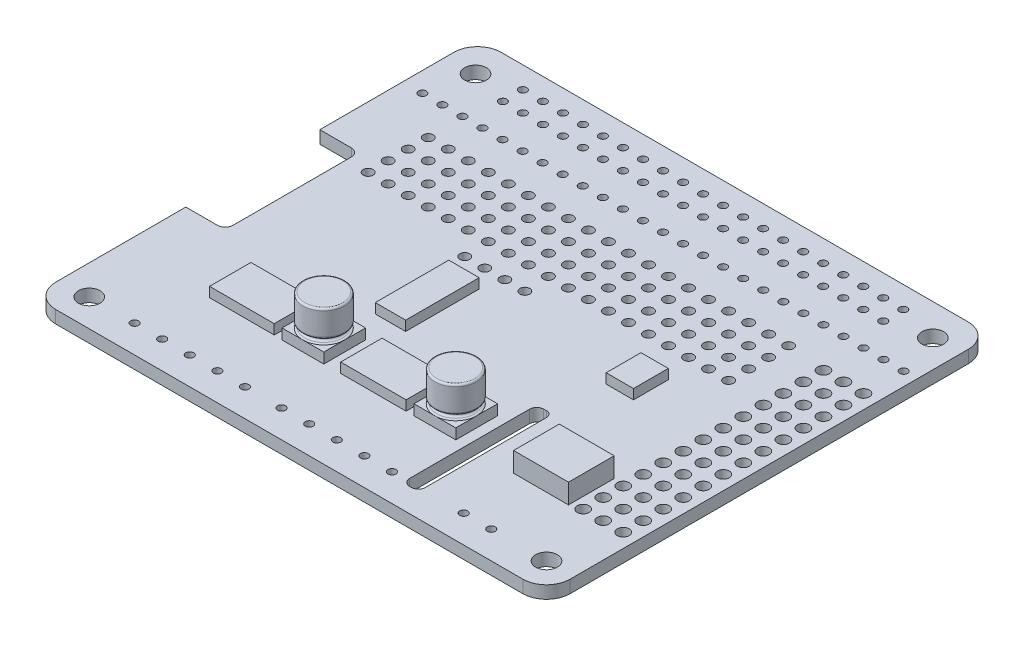
SolidWorks part; units mm, degrees
ref_plane "Front Plane" through (0, 0, 0) normal (0, 0, 1) x (1, 0, 0)
ref_plane "Top Plane" through (0, 0, 0) normal (0, 1, 0) x (1, 0, 0)
ref_plane "Right Plane" through (0, 0, 0) normal (1, 0, 0) x (0, 0, -1)
sketch "Sketch1" plane through (0, 0, 0) normal (0, 1, 0) x (1, 0, 0)
  line L1 (-72.0204, 27.4034) -> (-12.7704, 27.4034)
  line L2 (-75.0204, 24.4034) -> (-75.0204, -26.0966)
  line L3 (-72.0204, -29.0966) -> (-12.7704, -29.0966)
  line L4 (-9.7704, 24.4034) -> (-9.7704, -26.0966)
  line L5 (-75.0204, 7.4034) -> (-71.0204, 7.4034)
  line L6 (-75.0204, 7.4034) -> (-75.0204, -9.5966)
  line L7 (-75.0204, -9.5966) -> (-71.0204, -9.5966)
  line L8 (-70.0204, 6.4034) -> (-70.0204, -8.5966)
  line L9 (-29.7669, -9.0966) -> (-30.1204, -9.0966)
  line L10 (-29.0204, -9.8431) -> (-29.0204, -25.1966)
  line L11 (-29.9204, -26.0966) -> (-30.1204, -26.0966)
  line L12 (-31.0204, -9.9966) -> (-31.0204, -25.1966)
  arc A0 (-72.0204, -29.0966) -> (-75.0204, -26.0966) centre (-72.0204, -26.0966) cw
  arc A1 (-9.7704, -26.0966) -> (-12.7704, -29.0966) centre (-12.7704, -26.0966) cw
  arc A2 (-9.7704, 24.4034) -> (-12.7704, 27.4034) centre (-12.7704, 24.4034) ccw
  arc A3 (-72.0204, 27.4034) -> (-75.0204, 24.4034) centre (-72.0204, 24.4034) ccw
  arc A4 (-70.0204, -8.5966) -> (-71.0204, -9.5966) centre (-71.0204, -8.5966) cw
  arc A5 (-70.0204, 6.4034) -> (-71.0204, 7.4034) centre (-71.0204, 6.4034) ccw
  arc A6 (-29.0204, -25.1966) -> (-29.9204, -26.0966) centre (-29.9204, -25.1966) cw
  arc A7 (-30.1204, -26.0966) -> (-31.0204, -25.1966) centre (-30.1204, -25.1966) cw
  arc A8 (-30.1204, -9.0966) -> (-31.0204, -9.9966) centre (-30.1204, -9.9966) ccw
  arc A9 (-29.7669, -9.0966) -> (-29.0204, -9.8431) centre (-29.7669, -9.8431) cw
  circle A10 centre (-13.2704, -25.5966) radius 1.375
  circle A11 centre (-71.2704, -25.5966) radius 1.375
  circle A12 centre (-71.2704, 23.4034) radius 1.375
  circle A13 centre (-13.2704, 23.4034) radius 1.375
  point P6 (-75.0204, -29.0966)
  point P11 (-9.7704, 27.4034)
  point P14 (-75.0204, 27.4034)
  point P23 (-70.0204, 7.4034)
  point P30 (-29.0204, -26.0966)
  point P35 (-31.0204, -9.0966)
  point P38 (-29.0204, -9.0966)
  point P41 (0, 0)
  point P43 (0, 0)
  dimension "D3" = 3
  dimension "D7" = 1
  dimension "D12" = 0.9
  dimension "D13" = 0.7465
  dimension "D14" = 2.75
  dimension "D1" = 56.5
  dimension "D2" = 65.25
  dimension "D4" = 17
  dimension "D5" = 5
  dimension "D6" = 20
  dimension "D8" = 17
  dimension "D9" = 2
  dimension "D10" = 44
  dimension "D11" = 3
  dimension "D15" = 3.5
  dimension "D16" = 3.5
  dimension "D17" = 2
  dimension "D18" = 2
extrude "Board" add sketch "Sketch1" along normal blind 1.6 contours A5 L8 A4 L7 L2 A0 L3 A1 L4 A2 L1 A3 L5 A13 A12 A11 A10 L9 A9 L10 A6 L11 A7 L12 A8 region at (-41.7924, 0, 0.6811)
sketch "Sketch2" plane through (0, 1.6, 0) normal (0, 1, 0) x (1, 0, 0)
  line L8 (-70.0204, 6.4034) -> (-70.0204, -8.5966)
  line L9 (-71.0204, -9.5966) -> (-75.0204, -9.5966)
  line L10 (-75.0204, -9.5966) -> (-75.0204, -26.0966)
  line L11 (-72.0204, -29.0966) -> (-12.7704, -29.0966)
  line L12 (-9.7704, -26.0966) -> (-9.7704, 24.4034)
  line L13 (-12.7704, 27.4034) -> (-72.0204, 27.4034)
  line L14 (-75.0204, 24.4034) -> (-75.0204, 7.4034)
  line L15 (-75.0204, 7.4034) -> (-71.0204, 7.4034)
  line L16 (-70.0204, 6.4034) -> (-70.0204, -8.5966)
  line L17 (-71.0204, -9.5966) -> (-75.0204, -9.5966)
  line L18 (-75.0204, -9.5966) -> (-75.0204, -26.0966)
  line L19 (-72.0204, -29.0966) -> (-12.7704, -29.0966)
  line L20 (-9.7704, -26.0966) -> (-9.7704, 24.4034)
  line L21 (-12.7704, 27.4034) -> (-72.0204, 27.4034)
  line L22 (-75.0204, 24.4034) -> (-75.0204, 7.4034)
  line L23 (-75.0204, 7.4034) -> (-71.0204, 7.4034)
  circle A0 centre (-66.5204, 24.6534) radius 0.5
  circle A1 centre (-63.9804, 24.6534) radius 0.5
  circle A2 centre (-61.4404, 24.6534) radius 0.5
  circle A3 centre (-58.9004, 24.6534) radius 0.5
  circle A4 centre (-56.3604, 24.6534) radius 0.5
  circle A5 centre (-53.8204, 24.6534) radius 0.5
  arc A6 (-70.0204, 6.4034) -> (-71.0204, 7.4034) centre (-71.0204, 6.4034) ccw
  arc A7 (-71.0204, -9.5966) -> (-70.0204, -8.5966) centre (-71.0204, -8.5966) ccw
  arc A8 (-75.0204, -26.0966) -> (-72.0204, -29.0966) centre (-72.0204, -26.0966) ccw
  arc A9 (-12.7704, -29.0966) -> (-9.7704, -26.0966) centre (-12.7704, -26.0966) ccw
  arc A10 (-9.7704, 24.4034) -> (-12.7704, 27.4034) centre (-12.7704, 24.4034) ccw
  arc A11 (-72.0204, 27.4034) -> (-75.0204, 24.4034) centre (-72.0204, 24.4034) ccw
  arc A12 (-70.0204, 6.4034) -> (-71.0204, 7.4034) centre (-71.0204, 6.4034) ccw
  arc A13 (-71.0204, -9.5966) -> (-70.0204, -8.5966) centre (-71.0204, -8.5966) ccw
  arc A14 (-75.0204, -26.0966) -> (-72.0204, -29.0966) centre (-72.0204, -26.0966) ccw
  arc A15 (-12.7704, -29.0966) -> (-9.7704, -26.0966) centre (-12.7704, -26.0966) ccw
  arc A16 (-9.7704, 24.4034) -> (-12.7704, 27.4034) centre (-12.7704, 24.4034) ccw
  arc A17 (-72.0204, 27.4034) -> (-75.0204, 24.4034) centre (-72.0204, 24.4034) ccw
  circle A18 centre (-51.2804, 24.6534) radius 0.5
  circle A19 centre (-48.7404, 24.6534) radius 0.5
  circle A20 centre (-46.2004, 24.6534) radius 0.5
  circle A21 centre (-43.6604, 24.6534) radius 0.5
  circle A22 centre (-41.1204, 24.6534) radius 0.5
  circle A23 centre (-38.5804, 24.6534) radius 0.5
  circle A24 centre (-36.0404, 24.6534) radius 0.5
  circle A25 centre (-33.5004, 24.6534) radius 0.5
  circle A26 centre (-30.9604, 24.6534) radius 0.5
  circle A27 centre (-28.4204, 24.6534) radius 0.5
  circle A28 centre (-25.8804, 24.6534) radius 0.5
  circle A29 centre (-23.3404, 24.6534) radius 0.5
  circle A30 centre (-20.8004, 24.6534) radius 0.5
  circle A31 centre (-18.2604, 24.6534) radius 0.5
  circle A32 centre (-63.9804, 22.1134) radius 0.5
  circle A33 centre (-61.4404, 22.1134) radius 0.5
  circle A34 centre (-58.9004, 22.1134) radius 0.5
  circle A35 centre (-56.3604, 22.1134) radius 0.5
  circle A36 centre (-53.8204, 22.1134) radius 0.5
  circle A37 centre (-51.2804, 22.1134) radius 0.5
  circle A38 centre (-48.7404, 22.1134) radius 0.5
  circle A39 centre (-46.2004, 22.1134) radius 0.5
  circle A40 centre (-43.6604, 22.1134) radius 0.5
  circle A41 centre (-41.1204, 22.1134) radius 0.5
  circle A42 centre (-38.5804, 22.1134) radius 0.5
  circle A43 centre (-36.0404, 22.1134) radius 0.5
  circle A44 centre (-33.5004, 22.1134) radius 0.5
  circle A45 centre (-30.9604, 22.1134) radius 0.5
  circle A46 centre (-28.4204, 22.1134) radius 0.5
  circle A47 centre (-25.8804, 22.1134) radius 0.5
  circle A48 centre (-23.3404, 22.1134) radius 0.5
  circle A49 centre (-20.8004, 22.1134) radius 0.5
  circle A50 centre (-18.2604, 22.1134) radius 0.5
  circle A51 centre (-66.5204, 22.1134) radius 0.5
  circle A52 centre (-72.5204, 17.9034) radius 0.5
  circle A53 centre (-69.9766, 17.9034) radius 0.5
  circle A54 centre (-67.4329, 17.9034) radius 0.5
  circle A55 centre (-64.8891, 17.9034) radius 0.5
  circle A56 centre (-62.3454, 17.9034) radius 0.5
  circle A57 centre (-59.8016, 17.9034) radius 0.5
  circle A58 centre (-57.2579, 17.9034) radius 0.5
  circle A59 centre (-54.7141, 17.9034) radius 0.5
  circle A60 centre (-52.1704, 17.9034) radius 0.5
  circle A61 centre (-49.6266, 17.9034) radius 0.5
  circle A62 centre (-47.0829, 17.9034) radius 0.5
  circle A63 centre (-44.5391, 17.9034) radius 0.5
  circle A64 centre (-41.9954, 17.9034) radius 0.5
  circle A65 centre (-39.4516, 17.9034) radius 0.5
  circle A66 centre (-36.9079, 17.9034) radius 0.5
  circle A67 centre (-34.3641, 17.9034) radius 0.5
  circle A68 centre (-31.8204, 17.9034) radius 0.5
  circle A69 centre (-29.2766, 17.9034) radius 0.5
  circle A70 centre (-26.7329, 17.9034) radius 0.5
  circle A71 centre (-24.1891, 17.9034) radius 0.5
  circle A72 centre (-21.6454, 17.9034) radius 0.5
  circle A73 centre (-19.1016, 17.9034) radius 0.5
  circle A74 centre (-16.5579, 17.9034) radius 0.5
  circle A75 centre (-14.0141, 17.9034) radius 0.5
  circle A76 centre (-11.4704, 17.9034) radius 0.5
  circle A77 centre (-11.5604, 12.9034) radius 0.75
  circle A78 centre (-14.1004, 12.9034) radius 0.75
  circle A79 centre (-16.6404, 12.9034) radius 0.75
  circle A80 centre (-14.1004, 10.3634) radius 0.75
  circle A81 centre (-16.6404, 10.3634) radius 0.75
  circle A82 centre (-14.1004, 7.8234) radius 0.75
  circle A83 centre (-16.6404, 7.8234) radius 0.75
  circle A84 centre (-14.1004, 5.2834) radius 0.75
  circle A85 centre (-16.6404, 5.2834) radius 0.75
  circle A86 centre (-14.1004, 2.7434) radius 0.75
  circle A87 centre (-16.6404, 2.7434) radius 0.75
  circle A88 centre (-14.1004, 0.2034) radius 0.75
  circle A89 centre (-16.6404, 0.2034) radius 0.75
  circle A90 centre (-14.1004, -2.3366) radius 0.75
  circle A91 centre (-16.6404, -2.3366) radius 0.75
  circle A92 centre (-14.1004, -4.8766) radius 0.75
  circle A93 centre (-16.6404, -4.8766) radius 0.75
  circle A94 centre (-14.1004, -7.4166) radius 0.75
  circle A95 centre (-16.6404, -7.4166) radius 0.75
  circle A96 centre (-14.1004, -9.9566) radius 0.75
  circle A97 centre (-16.6404, -9.9566) radius 0.75
  circle A98 centre (-14.1004, -12.4966) radius 0.75
  circle A99 centre (-16.6404, -12.4966) radius 0.75
  circle A100 centre (-14.1004, -15.0366) radius 0.75
  circle A101 centre (-16.6404, -15.0366) radius 0.75
  circle A102 centre (-14.1004, -17.5766) radius 0.75
  circle A103 centre (-16.6404, -17.5766) radius 0.75
  circle A104 centre (-11.5604, 10.3634) radius 0.75
  circle A105 centre (-11.5604, 7.8234) radius 0.75
  circle A106 centre (-11.5604, 5.2834) radius 0.75
  circle A107 centre (-11.5604, 2.7434) radius 0.75
  circle A108 centre (-11.5604, 0.2034) radius 0.75
  circle A109 centre (-11.5604, -2.3366) radius 0.75
  circle A110 centre (-11.5604, -4.8766) radius 0.75
  circle A111 centre (-11.5604, -7.4166) radius 0.75
  circle A112 centre (-11.5604, -9.9566) radius 0.75
  circle A113 centre (-11.5604, -12.4966) radius 0.75
  circle A114 centre (-11.5604, -15.0366) radius 0.75
  circle A115 centre (-11.5604, -17.5766) radius 0.75
  circle A116 centre (-67.2704, 13.4034) radius 0.625
  circle A117 centre (-64.7304, 13.4034) radius 0.625
  circle A118 centre (-62.1904, 13.4034) radius 0.625
  circle A119 centre (-59.6504, 13.4034) radius 0.625
  circle A120 centre (-57.1104, 13.4034) radius 0.625
  circle A121 centre (-54.5704, 13.4034) radius 0.625
  circle A122 centre (-52.0304, 13.4034) radius 0.625
  circle A123 centre (-49.4904, 13.4034) radius 0.625
  circle A124 centre (-46.9504, 13.4034) radius 0.625
  circle A125 centre (-44.4104, 13.4034) radius 0.625
  circle A126 centre (-41.8704, 13.4034) radius 0.625
  circle A127 centre (-39.3304, 13.4034) radius 0.625
  circle A128 centre (-36.7904, 13.4034) radius 0.625
  circle A129 centre (-34.2504, 13.4034) radius 0.625
  circle A130 centre (-31.7104, 13.4034) radius 0.625
  circle A131 centre (-29.1704, 13.4034) radius 0.625
  circle A132 centre (-26.6304, 13.4034) radius 0.625
  circle A133 centre (-24.0904, 13.4034) radius 0.625
  circle A134 centre (-21.5504, 13.4034) radius 0.625
  circle A135 centre (-64.7304, 10.8634) radius 0.625
  circle A136 centre (-62.1904, 10.8634) radius 0.625
  circle A137 centre (-59.6504, 10.8634) radius 0.625
  circle A138 centre (-57.1104, 10.8634) radius 0.625
  circle A139 centre (-54.5704, 10.8634) radius 0.625
  circle A140 centre (-52.0304, 10.8634) radius 0.625
  circle A141 centre (-49.4904, 10.8634) radius 0.625
  circle A142 centre (-46.9504, 10.8634) radius 0.625
  circle A143 centre (-44.4104, 10.8634) radius 0.625
  circle A144 centre (-41.8704, 10.8634) radius 0.625
  circle A145 centre (-39.3304, 10.8634) radius 0.625
  circle A146 centre (-36.7904, 10.8634) radius 0.625
  circle A147 centre (-34.2504, 10.8634) radius 0.625
  circle A148 centre (-31.7104, 10.8634) radius 0.625
  circle A149 centre (-29.1704, 10.8634) radius 0.625
  circle A150 centre (-26.6304, 10.8634) radius 0.625
  circle A151 centre (-24.0904, 10.8634) radius 0.625
  circle A152 centre (-21.5504, 10.8634) radius 0.625
  circle A153 centre (-64.7304, 8.3234) radius 0.625
  circle A154 centre (-62.1904, 8.3234) radius 0.625
  circle A155 centre (-59.6504, 8.3234) radius 0.625
  circle A156 centre (-57.1104, 8.3234) radius 0.625
  circle A157 centre (-54.5704, 8.3234) radius 0.625
  circle A158 centre (-52.0304, 8.3234) radius 0.625
  circle A159 centre (-49.4904, 8.3234) radius 0.625
  circle A160 centre (-46.9504, 8.3234) radius 0.625
  circle A161 centre (-44.4104, 8.3234) radius 0.625
  circle A162 centre (-41.8704, 8.3234) radius 0.625
  circle A163 centre (-39.3304, 8.3234) radius 0.625
  circle A164 centre (-36.7904, 8.3234) radius 0.625
  circle A165 centre (-34.2504, 8.3234) radius 0.625
  circle A166 centre (-31.7104, 8.3234) radius 0.625
  circle A167 centre (-29.1704, 8.3234) radius 0.625
  circle A168 centre (-26.6304, 8.3234) radius 0.625
  circle A169 centre (-24.0904, 8.3234) radius 0.625
  circle A170 centre (-21.5504, 8.3234) radius 0.625
  circle A171 centre (-64.7304, 5.7834) radius 0.625
  circle A172 centre (-62.1904, 5.7834) radius 0.625
  circle A173 centre (-59.6504, 5.7834) radius 0.625
  circle A174 centre (-57.1104, 5.7834) radius 0.625
  circle A175 centre (-54.5704, 5.7834) radius 0.625
  circle A176 centre (-52.0304, 5.7834) radius 0.625
  circle A177 centre (-49.4904, 5.7834) radius 0.625
  circle A178 centre (-46.9504, 5.7834) radius 0.625
  circle A179 centre (-44.4104, 5.7834) radius 0.625
  circle A180 centre (-41.8704, 5.7834) radius 0.625
  circle A181 centre (-39.3304, 5.7834) radius 0.625
  circle A182 centre (-36.7904, 5.7834) radius 0.625
  circle A183 centre (-34.2504, 5.7834) radius 0.625
  circle A184 centre (-31.7104, 5.7834) radius 0.625
  circle A185 centre (-29.1704, 5.7834) radius 0.625
  circle A186 centre (-26.6304, 5.7834) radius 0.625
  circle A187 centre (-24.0904, 5.7834) radius 0.625
  circle A188 centre (-21.5504, 5.7834) radius 0.625
  circle A189 centre (-67.2704, 10.8634) radius 0.625
  circle A190 centre (-67.2704, 8.3234) radius 0.625
  circle A191 centre (-67.2704, 5.7834) radius 0.625
  circle A192 centre (-44.2704, 2.6534) radius 0.625
  circle A193 centre (-46.8104, 2.6534) radius 0.625
  circle A194 centre (-49.3504, 2.6534) radius 0.625
  circle A195 centre (-51.8904, 2.6534) radius 0.625
  circle A196 centre (-20.2704, -25.5966) radius 0.5
  circle A197 centre (-23.7704, -25.5966) radius 0.5
  circle A198 centre (-32.8704, -25.5966) radius 0.5
  circle A199 centre (-36.3704, -25.5966) radius 0.5
  circle A200 centre (-39.8704, -25.5966) radius 0.5
  circle A201 centre (-43.3704, -25.5966) radius 0.5
  circle A202 centre (-46.8704, -25.5966) radius 0.5
  circle A203 centre (-65.5204, -25.5966) radius 0.5
  circle A204 centre (-62.0204, -25.5966) radius 0.5
  circle A205 centre (-58.5204, -25.5966) radius 0.5
  circle A206 centre (-55.0204, -25.5966) radius 0.5
  circle A207 centre (-51.5204, -25.5966) radius 0.5
  dimension "D2" = 2.75
  dimension "D6" = 2.5
  dimension "D9" = 1.5
  dimension "D12" = 3
  dimension "D14" = 14
  dimension "D18" = 34.5
  dimension "D21" = 3.5
  dimension "D24" = 3.5
  dimension "D27" = 9.5
  dimension "D3" = 8.5
  dimension "D7" = 10.5
  dimension "D10" = 14.5
  dimension "D11" = 1.7
  dimension "D15" = 2.75
  dimension "D19" = 31.75
  dimension "D22" = 10.5
  dimension "D25" = 23.1
  dimension "D28" = 3.5
  dimension "D1" = 0
  dimension "D4" = 20
  dimension "D5" = 2
  dimension "D8" = 25
  dimension "D13" = 13
  dimension "D16" = 19
  dimension "D17" = 4
  dimension "D20" = 4
  dimension "D23" = 2
  dimension "D26" = 5
  dimension "D29" = 5
extrude "Some Holes" cut sketch "Sketch2" against normal blind 1.6 contours A114 | A83 | A103 | A102 | A115 | A100 | A101 | A99 | A98 | A113 | A112 | A96 | A97 | A95 | A94 | A111 | A110 | A92 | A93 | A91 | A90 | A109 | A108 | A88 | A89 | A87 | A86 | A107 | A106 | A84 | A85 | A82 | A105 | A104 | A77 | A80 | A81 | A79 | A78 | A76 | A75 | A74 | A73 | A72 | A50 | A31 | A49 | A30 | A48 | A29 | A71 | A70 | A47 | A28 | A27 | A46 | A69 | A68 | A45 | A26 | A67 | A44 | A25 | A66 | A43 | A24 | A65 | A42 | A23 | A64 | A41 | A22 | A63 | A40 | A21 | A20 | A39 | A62 | A61 | A38 | A19 | A18 | A37 | A60 | A59 | A36 | A5 | A4 | A35 | A58 | A57 | A34 | A3 | A2 | A33 | A56 | A55 | A32 | A1 | A0 region at (-16.6404, 1.6, -7.8234) region at (-11.5604, 1.6, 15.0366)
extrude "Remaining Holes" cut sketch "Sketch2<4>" against normal blind 1.6 contours A51 | A54 | A53 | A52 | A116 | A117 | A118 | A119 | A120 | A121 | A122 | A123 | A124 | A125 | A126 | A127 | A128 | A129 | A130 | A131 | A132 | A133 | A134 | A152 | A170 | A188 | A187 | A169 | A151 | A150 | A168 | A186 | A167 | A185 | A149 | A148 | A166 | A184 | A183 | A165 | A147 | A146 | A164 | A182 | A181 | A163 | A145 | A144 | A162 | A180 | A192 | A193 | A194 | A195 | A179 | A161 | A143 | A142 | A160 | A178 | A177 | A159 | A141 | A140 | A158 | A176 | A175 | A157 | A139 | A138 | A156 | A174 | A173 | A155 | A137 | A136 | A154 | A172 | A171 | A153 | A135 | A189 | A190 | A191 | A196 | A197 | A198 | A199 | A200 | A201 | A202 | A207 | A206 | A205 | A204 | A203
sketch "Sketch2<4>" plane through (0, 1.6, 0) normal (0, 1, 0) x (1, 0, 0) same geometry as "Sketch2"
sketch "Sketch3" plane through (0, 1.6, 0) normal (0, 1, 0) x (1, 0, 0)
  line L1 (-63.5566, -12.7994) -> (-55.3553, -12.7994)
  line L2 (-63.5566, -12.7994) -> (-63.5566, -18.049)
  line L3 (-63.5566, -18.049) -> (-55.3553, -18.049)
  line L4 (-55.3553, -12.7994) -> (-55.3553, -18.049)
  line L5 (-46.9235, -12.7994) -> (-38.6242, -12.7994)
  line L6 (-46.9235, -12.7994) -> (-46.9235, -18.049)
  line L7 (-46.9235, -18.049) -> (-38.6242, -18.049)
  line L8 (-38.6242, -12.7994) -> (-38.6242, -18.049)
  line L9 (-24.9943, -12.2493) -> (-18.0305, -12.2493)
  line L10 (-24.9943, -12.2493) -> (-24.9943, -18.049)
  line L11 (-24.9943, -18.049) -> (-18.0305, -18.049)
  line L12 (-18.0305, -12.2493) -> (-18.0305, -18.049)
  line L13 (-28.9097, 2.0257) -> (-25.4441, 2.0257)
  line L14 (-28.9097, 2.0257) -> (-28.9097, -2.3878)
  line L15 (-28.9097, -2.3878) -> (-25.4441, -2.3878)
  line L16 (-25.4441, 2.0257) -> (-25.4441, -2.3878)
  line L17 (-51.2629, 0) -> (-47.4092, 0)
  line L18 (-51.2629, 0) -> (-51.2629, -9.3248)
  line L19 (-51.2629, -9.3248) -> (-47.4092, -9.3248)
  line L20 (-47.4092, 0) -> (-47.4092, -9.3248)
  dimension "D1" = 5.2496
  dimension "D2" = 8.2013
  dimension "D3" = 5.2496
  dimension "D4" = 8.2993
  dimension "D5" = 5.7997
  dimension "D6" = 6.9638
  dimension "D7" = 4.4135
  dimension "D8" = 3.4656
  dimension "D9" = 9.3248
  dimension "D10" = 3.8537
extrude "ICs" add sketch "Sketch3" along normal blind 1.25 contours L8 L5 L6 L7 | L4 L1 L2 L3 | L16 L13 L14 L15 | L18 L17 L20 L19 region at (-59.456, 1.6, 15.4242) region at (-42.7739, 1.6, 15.4242) region at (-27.1769, 1.6, 0.181)
extrude "Voltage Regulator" add sketch "Sketch3<5>" along normal blind 2.5 contours L11 L12 L9 L10
sketch "Sketch3<5>" plane through (0, 1.6, 0) normal (0, 1, 0) x (1, 0, 0) same geometry as "Sketch3"
sketch "Sketch4" plane through (0, 1.6, 0) normal (0, 1, 0) x (1, 0, 0)
  line L0 (-31.0204, -9.9966) -> (-31.0204, -25.1966) construction
  line L1 (-54.3204, -18.0966) -> (-49.0204, -18.0966)
  line L2 (-54.3204, -18.0966) -> (-54.3204, -12.7966)
  line L3 (-54.3204, -12.7966) -> (-49.0204, -12.7966)
  line L4 (-49.0204, -18.0966) -> (-49.0204, -12.7966)
  line L5 (-32.3204, -18.0544) -> (-37.6204, -18.0544)
  line L6 (-32.3204, -18.0544) -> (-32.3204, -12.7544)
  line L7 (-32.3204, -12.7544) -> (-37.6204, -12.7544)
  line L8 (-37.6204, -18.0544) -> (-37.6204, -12.7544)
  line L9 (-72.0204, -29.0966) -> (-12.7704, -29.0966) construction
  dimension "D1" = 5.3
  dimension "D2" = 5.3
  dimension "D3" = 5.3
  dimension "D4" = 5.3
  dimension "D5" = 11.4
  dimension "D6" = 1.3
  dimension "D7" = 11
extrude "Cap Base" add sketch "Sketch4" along normal blind 1.32
sketch "Sketch5" plane through (0, 2.92, 0) normal (0, 1, 0) x (1, 0, 0)
  line L0 (-54.3204, -15.4466) -> (-49.0204, -15.4466)
  line L1 (-51.6704, -12.7966) -> (-51.6704, -18.0966)
  line L2 (-34.9704, -12.7544) -> (-34.9704, -18.0544)
  line L3 (-37.6204, -15.4044) -> (-32.3204, -15.4044)
  line L4 (-54.3204, -12.7966) -> (-54.3204, -18.0966)
  line L5 (-54.3204, -18.0966) -> (-49.0204, -18.0966)
  line L6 (-49.0204, -18.0966) -> (-49.0204, -12.7966)
  line L7 (-49.0204, -12.7966) -> (-54.3204, -12.7966)
  line L8 (-54.3204, -12.7966) -> (-54.3204, -18.0966)
  line L9 (-54.3204, -18.0966) -> (-49.0204, -18.0966)
  line L10 (-49.0204, -18.0966) -> (-49.0204, -12.7966)
  line L11 (-49.0204, -12.7966) -> (-54.3204, -12.7966)
  line L12 (-32.3204, -18.0544) -> (-32.3204, -12.7544)
  line L13 (-32.3204, -12.7544) -> (-37.6204, -12.7544)
  line L14 (-37.6204, -12.7544) -> (-37.6204, -18.0544)
  line L15 (-37.6204, -18.0544) -> (-32.3204, -18.0544)
  line L16 (-32.3204, -18.0544) -> (-32.3204, -12.7544)
  line L17 (-32.3204, -12.7544) -> (-37.6204, -12.7544)
  line L18 (-37.6204, -12.7544) -> (-37.6204, -18.0544)
  line L19 (-37.6204, -18.0544) -> (-32.3204, -18.0544)
  circle A0 centre (-51.6704, -15.4466) radius 2.65
  circle A1 centre (-34.9704, -15.4044) radius 2.65
  line M9 (-54.3204, -12.7966) -> (-54.3204, -18.0966)
  line M10 (-54.3204, -18.0966) -> (-49.0204, -18.0966)
  dimension "D1" = 0
  dimension "D2" = 0
extrude "Cap1" add sketch "Sketch5" along normal blind 0.1 contours L1 A0 L0 | L0 A0 L1 | A0 L10 L0 L1 M10 | A0 L9 L1 L0 M9 | L2 A1 L3 | L3 A1 L2 | L19 A1 L16 L3 L2 | L18 A1 L19 L2 L3 region at (-52.7951, 2.92, 14.3219) region at (-52.7951, 2.92, 16.5713) region at (-50.5457, 2.92, 14.3219) region at (-50.5457, 2.92, 16.5713) region at (-33.8457, 2.92, 14.2797) region at (-36.0951, 2.92, 14.2797) region at (-33.8457, 2.92, 16.5291) region at (-36.0951, 2.92, 16.5291)
sketch "Sketch8" plane through (0, 3.02, 0) normal (0, 1, 0) x (1, 0, 0)
  circle A0 centre (-34.9704, -15.4044) radius 2.65 construction
  circle A1 centre (-51.6704, -15.4466) radius 2.65 construction
  circle A2 centre (-34.9704, -15.4044) radius 2.65
  circle A3 centre (-51.6704, -15.4466) radius 2.65
  circle A4 centre (-51.6704, -15.4466) radius 2.15
  circle A5 centre (-34.9704, -15.4044) radius 2.15
extrude "Cap2" add sketch "Sketch8" along normal blind 0.5 contours A5 | A4 | A5 region at (-34.9704, 3.02, 15.4044)
sketch "Sketch9" plane through (0, 3.52, 0) normal (0, 1, 0) x (1, 0, 0)
  circle A0 centre (-34.9704, -15.4044) radius 2.15 construction
  circle A1 centre (-51.6704, -15.4466) radius 2.15 construction
  circle A2 centre (-34.9704, -15.4044) radius 2.65 construction
  circle A3 centre (-51.6704, -15.4466) radius 2.65 construction
  circle A4 centre (-34.9704, -15.4044) radius 2.15
  circle A5 centre (-51.6704, -15.4466) radius 2.15
  circle A6 centre (-34.9704, -15.4044) radius 2.65
  circle A7 centre (-51.6704, -15.4466) radius 2.65
  circle A8 centre (-51.6704, -15.4466) radius 2.65
  circle A9 centre (-34.9704, -15.4044) radius 2.65
  circle M1 centre (-51.6704, -15.4466) radius 2.15
extrude "Cap3" add sketch "Sketch9" along normal blind 3.38 contours M1 | A7 M1 | A4 | A6 A4 region at (-34.9704, 3.52, 15.4044) region at (-51.6704, 3.52, 15.4466) region at (-37.5454, 3.52, 15.4044) region at (-54.2454, 3.52, 15.4466)
fillet "Cap4" radius 0.24 2 edges at (-51.6704, 6.9, 18.0966) (-34.9704, 6.9, 18.0544)
fillet "Cap5" radius 0.25 4 edges at (-34.9704, 3.52, 17.5544) (-34.9704, 3.02, 17.5544) (-51.6704, 3.52, 17.5966) (-51.6704, 3.02, 17.5966)
fillet "Cap6" radius 0.25 2 edges at (-34.9704, 3.52, 18.0544) (-51.6704, 3.52, 18.0966)
fillet "Cap7" radius 0.1 2 edges at (-51.6704, 3.02, 18.0966) (-34.9704, 3.02, 18.0544) second distance 0.25 first distance on face at (-51.6704, 3.02, 18.0966) first distance on face at (-34.9704, 3.02, 18.0544)
